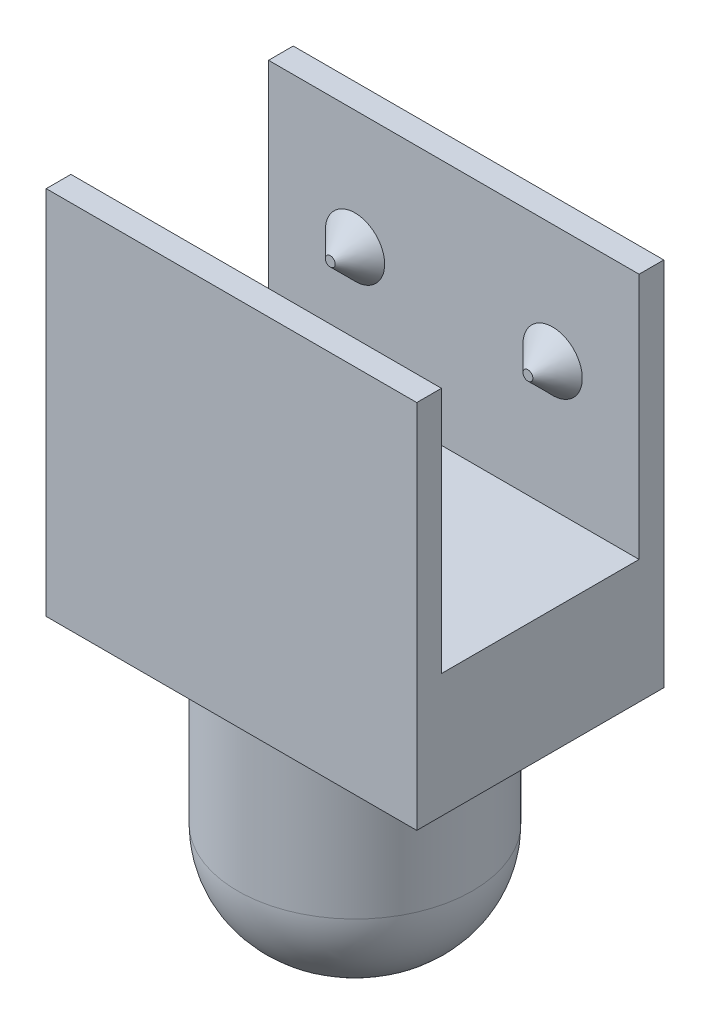
SolidWorks part; units mm, degrees
ref_plane "Front Plane" through (0, 0, 0) normal (0, 0, 1) x (1, 0, 0)
ref_plane "Top Plane" through (0, 0, 0) normal (0, 1, 0) x (1, 0, 0)
ref_plane "Right Plane" through (0, 0, 0) normal (1, 0, 0) x (0, 0, -1)
sketch "Sketch1" plane through (0, 0, 0) normal (0, 0, 1) x (1, 0, 0)
  line L0 (0, 0) -> (19.05, 0)
  line L1 (19.05, 0) -> (19.05, -19.05)
  line L2 (19.05, -19.05) -> (0, -19.05)
  line L3 (0, -19.05) -> (0, 0)
  point P3 (0, 0)
  point P5 (0, 0)
  dimension "D1" = 19.05
  dimension "D2" = 19.05
extrude "Boss-Extrude1" add sketch "Sketch1" along normal mid plane 12.7
sketch "Sketch2" plane through (0, 0, 0) normal (0, 0, 1) x (1, 0, 0)
  line L0 (0, -12.7) -> (19.05, -12.7)
  line L1 (0, 0) -> (0, -19.05) construction
  line L2 (19.05, -19.05) -> (19.05, 0) construction
  line L3 (19.05, -12.7) -> (19.05, 0)
  line L4 (19.05, 0) -> (0, 0)
  line L5 (0, 0) -> (0, -12.7)
  dimension "D1" = 12.7
extrude "Cut-Extrude1" cut sketch "Sketch2" against normal mid plane 10.16
sketch "Sketch3" plane through (0, 0, -5.08) normal (0, 0, 1) x (1, 0, 0)
  line L0 (14.605, -6.096) -> (4.445, -6.096) construction
  line L1 (4.445, -6.096) -> (4.445, -12.7) construction
  line L2 (0, -12.7) -> (19.05, -12.7) construction
  line L3 (14.605, -6.096) -> (14.605, -12.7) construction
  line L4 (9.525, -6.096) -> (9.525, -12.7) construction
  circle A0 centre (14.605, -6.096) radius 1.524
  circle A1 centre (4.445, -6.096) radius 1.524
  dimension "D2" = 3.048
  dimension "D1" = 6.604
  dimension "D3" = 10.16
extrude "Boss-Extrude2" add sketch "Sketch3" along normal blind 1.27
chamfer "Chamfer1" distance 1.27 angle 45 2 edges at (16.129, -6.096, -3.81) (5.969, -6.096, -3.81)
mirror "Mirror1" about plane through (0, 0, 0) normal (0, 0, 1) of "Chamfer1", "Boss-Extrude2"
sketch "Sketch4" plane through (0, -19.05, 0) normal (0, -1, 0) x (1, 0, 0)
  line L0 (0, 0) -> (9.525, 0) construction
  line L1 (0, 6.35) -> (0, -6.35) construction
  line L2 (9.525, 0) -> (9.525, 6.35) construction
  line L3 (0, 6.35) -> (19.05, 6.35) construction
  circle A0 centre (9.525, 0) radius 6.0325
  dimension "D1" = 12.065
extrude "Boss-Extrude3" add sketch "Sketch4" along normal blind 12.7
fillet "Fillet1" radius 5.08 1 edges at (15.5575, -31.75, 0)
